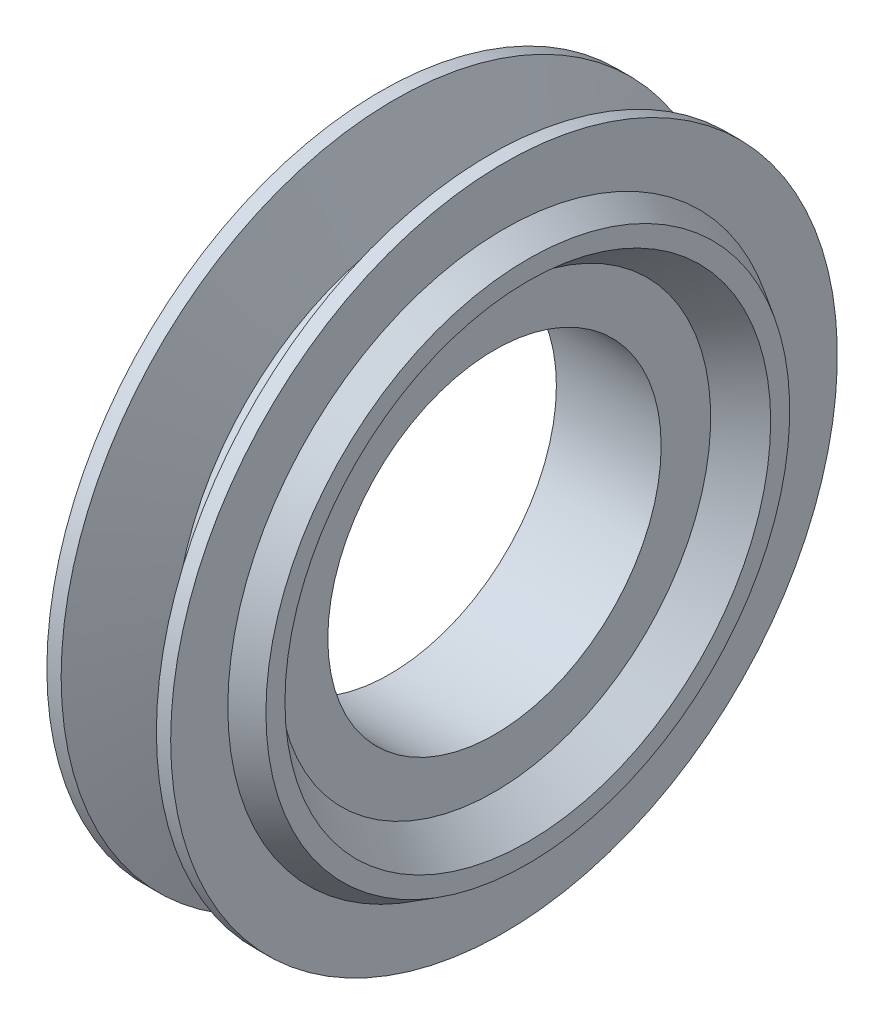
SolidWorks part; units mm, degrees
material "Обычная углеродистая сталь"
ref_plane "Спереди" through (0, 0, 0) normal (0, 0, 1) x (1, 0, 0)
ref_plane "Сверху" through (0, 0, 0) normal (0, 1, 0) x (1, 0, 0)
ref_plane "Справа" through (0, 0, 0) normal (1, 0, 0) x (0, 0, -1)
sketch "Эскиз1" plane through (0, 0, 0) normal (0, 0, 1) x (1, 0, 0)
  line L0 (-55.5492, 0) -> (55.5492, 0) construction
  line L1 (5.5, 0) -> (5.5, 22.7)
  line L2 (5.5, 22.7) -> (9, 25.5)
  line L3 (9, 25.5) -> (9, 27.5)
  line L4 (9, 27.5) -> (6.5, 29)
  line L5 (6.5, 29) -> (6.5, 35)
  line L6 (6.5, 35) -> (5, 35)
  line L7 (5, 35) -> (1, 22.7)
  line L8 (1, 22.7) -> (-1, 22.7)
  line L9 (-1, 22.7) -> (-5, 35)
  line L10 (-5, 35) -> (-6.5, 35)
  line L11 (-6.5, 35) -> (-6.5, 29)
  line L12 (-6.5, 29) -> (-9, 27.5)
  line L13 (-9, 27.5) -> (-9, 25.5)
  line L14 (-9, 25.5) -> (-5.5, 22.7)
  line L15 (-5.5, 22.7) -> (-5.5, 0)
  line L16 (0, 0) -> (0, 45.4) construction
  line L17 (-5.5, 0) -> (5.5, 0)
  point P21 (0, 22.7)
  dimension "D1" = 2
  dimension "D2" = 12.3
  dimension "D3" = 1.5
  dimension "D4" = 10
  dimension "D5" = 5
  dimension "D6" = 6
  dimension "D7" = 13
  dimension "D8" = 18
  dimension "D9" = 2
  dimension "D10" = 9.5
  dimension "D11" = 35
  dimension "D12" = 9
  dimension "D13" = 11
  dimension "D14" = 5.5
revolve "Повернуть1" add sketch "Эскиз1" angle 360 about L0
sketch "Эскиз2" plane through (5.5, 0, 0) normal (1, 0, 0) x (0, 0, -1)
  circle A0 centre (0, 0) radius 17.5
  dimension "D1" = 35
extrude "Вырез-Вытянуть1" cut sketch "Эскиз2" against normal through all
sketch "Эскиз4" plane through (0, 0, 0) normal (0, 0, 1) x (1, 0, 0)
  line L0 (0, 0) -> (0, 45.4) construction
  line L1 (-2.8374, 26) -> (2.8374, 26)
  line L2 (-2.8374, 26) -> (-2.8374, 21.1262)
  line L3 (-2.8374, 21.1262) -> (2.8374, 21.1262)
  line L4 (2.8374, 26) -> (2.8374, 21.1262)
  line L5 (-2.8374, 26) -> (2.8374, 21.1262) construction
  line L6 (-2.8374, 21.1262) -> (2.8374, 26) construction
  line L7 (6.5, 35) -> (5, 35) construction
  point P0 (0, 23.5631)
  dimension "D1" = 9
revolve "Повернуть2" add sketch "Эскиз4" angle 360 about L0
